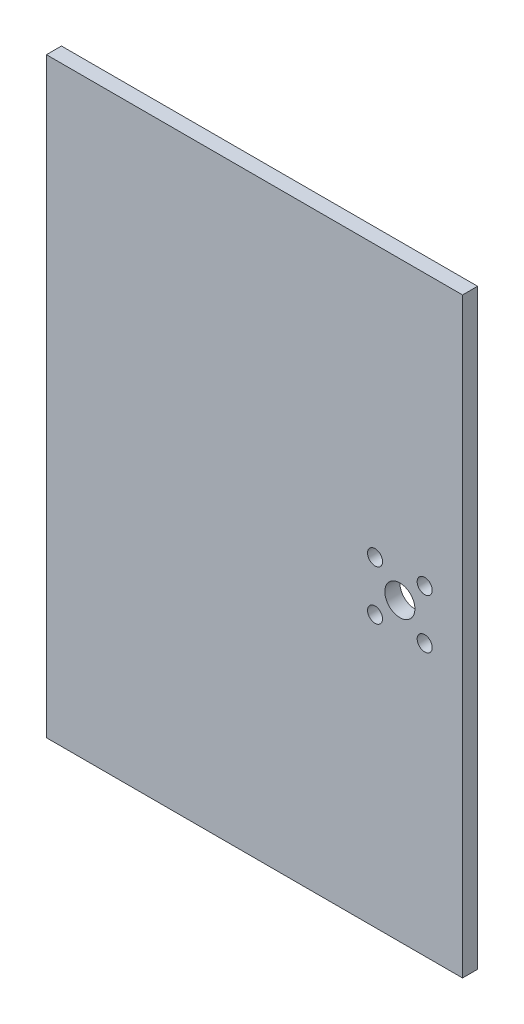
SolidWorks part; units mm, degrees
ref_plane "前视基准面" through (0, 0, 0) normal (0, 0, 1) x (1, 0, 0)
ref_plane "上视基准面" through (0, 0, 0) normal (0, 1, 0) x (1, 0, 0)
ref_plane "右视基准面" through (0, 0, 0) normal (1, 0, 0) x (0, 0, -1)
other "Configuration Table"
sketch "草图1" plane through (0, 0, 0) normal (0, 0, 1) x (1, 0, 0)
  line L1 (41.5, -59) -> (-41.5, -59)
  line L2 (41.5, -59) -> (41.5, 59)
  line L3 (41.5, 59) -> (-41.5, 59)
  line L4 (-41.5, -59) -> (-41.5, 59)
  line L5 (41.5, -59) -> (-41.5, 59) construction
  line L6 (41.5, 59) -> (-41.5, -59) construction
  point P0 (0, 0)
  dimension "D1" = 118
  dimension "D2" = 83
extrude "凸台-拉伸1" add sketch "草图1" along normal blind 3
sketch "草图2" plane through (0, 0, 0) normal (0, 0, -1) x (-1, 0, 0)
  line L0 (-41.5, -59) -> (-41.5, 59) construction
  line L1 (-41.5, 59) -> (41.5, 59) construction
  circle A0 centre (-33.9497, 4.9497) radius 1.5
  circle A1 centre (-24.0503, 4.9497) radius 1.5
  circle A2 centre (-29, 0) radius 3
  circle A3 centre (-33.9497, -4.9497) radius 1.5
  circle A4 centre (-24.0503, -4.9497) radius 1.5
  dimension "D1" = 9.8995
  dimension "D2" = 7.5503
  dimension "D3" = 12.5
  dimension "D4" = 7.5503
  dimension "D5" = 4.9497
  dimension "D6" = 9.8995
  dimension "D7" = 4.9497
  dimension "D8" = 4.9497
  dimension "D9" = 4.9497
  dimension "D10" = 54.0503
extrude "切除-拉伸1" cut sketch "草图2" against normal blind 3
